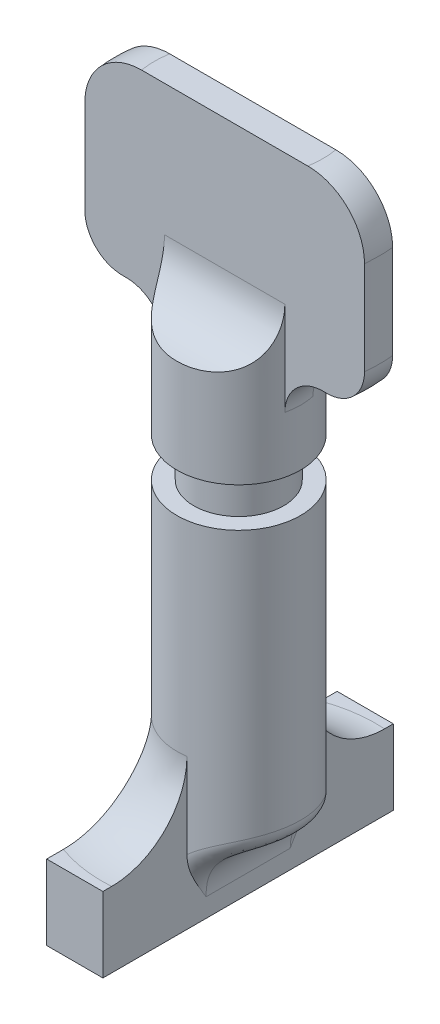
SolidWorks part; units mm, degrees
ref_plane "Front Plane" through (0, 0, 0) normal (0, 0, 1) x (1, 0, 0)
ref_plane "Top Plane" through (0, 0, 0) normal (0, 1, 0) x (1, 0, 0)
ref_plane "Right Plane" through (0, 0, 0) normal (1, 0, 0) x (0, 0, -1)
sketch "Sketch1" plane through (0, 0, 0) normal (0, 0, 1) x (1, 0, 0)
  line L0 (3.3, 27) -> (3.3, 22)
  line L1 (3.3, 22) -> (2.4, 22)
  line L2 (2.4, 22) -> (2.4, 19.9)
  line L3 (2.4, 19.9) -> (3.3, 19.9)
  line L4 (3.3, 19.9) -> (3.3, 5)
  line L5 (3.3, 5) -> (0, 5)
  line L6 (3.3, 27) -> (0, 27)
  line L7 (0, 27) -> (0, 5)
  dimension "D1" = 22
  dimension "D2" = 2.1
  dimension "D3" = 5
  dimension "D4" = 5
  dimension "D5" = 3.3
  dimension "D6" = 2.4
revolve "Revolve1" add sketch "Sketch1" angle 360 about L7
sketch "Sketch2" plane through (0, 27, 0) normal (0, 1, 0) x (1, 0, 0)
  line L1 (-11.4046, 0.75) -> (11.4046, 0.75)
  line L2 (-11.4046, 0.75) -> (-11.4046, -0.75)
  line L3 (-11.4046, -0.75) -> (11.4046, -0.75)
  line L4 (11.4046, 0.75) -> (11.4046, -0.75)
  line L5 (-11.4046, 0.75) -> (11.4046, -0.75) construction
  line L6 (-11.4046, -0.75) -> (11.4046, 0.75) construction
  circle A0 centre (0, 0) radius 3.3
  circle A1 centre (0, 0) radius 7.5
  circle A2 centre (0, 0) radius 3.3 construction
  circle M3 centre (0, 0) radius 3.3
  dimension "D2" = 15
  dimension "D1" = 1.5
extrude "Boss-Extrude1" add sketch "Sketch2" along normal blind 10 contours L3 L1 M3 | L1 A1 L3 M3 | L3 A1 L1 M3 region at (-5.3794, 27, 0) region at (0, 27, 0) region at (5.3794, 27, 0)
fillet "Fillet2" radius 2 4 edges at (7.5, 27, 0) (-7.5, 27, 0) (-3.3, 27, 0) (3.3, 27, 0)
fillet "Fillet3" radius 3 4 edges at (-7.5, 37, 0) (7.5, 37, 0) (0, 27, -0.75) (0, 27, 0.75)
sketch "Sketch21" plane through (0, 0, 0) normal (0, 1, 0) x (1, 0, 0)
  line L0 (0.5, 8.3) -> (0.5, -8.3) construction
  line L1 (0.5, -8.3) -> (-2.5, -8.3) construction
  line L2 (-2.5, -8.3) -> (-2.5, 8.3) construction
  line L3 (-2.5, 8.3) -> (0.5, 8.3) construction
  circle A0 centre (0, 0) radius 8 construction
  point P5 (0.5, 0)
  dimension "D1" = 16
  dimension "D2" = 16.6
  dimension "D3" = 3
  dimension "D4" = 8.5
sketch "Sketch5" plane through (0, 5, 0) normal (0, -1, 0) x (1, 0, 0)
  line L1 (-1.925, -7.75) -> (-0.075, -7.75) construction
  line L2 (-1.925, -7.75) -> (-1.925, 7.75) construction
  line L3 (-1.925, 7.75) -> (-0.075, 7.75) construction
  line L4 (-0.075, -7.75) -> (-0.075, 7.75) construction
  line L5 (-0.075, 0) -> (-1.925, 0) construction
  line L6 (-1, 23.25) -> (-1, -7.75) construction
  line L11 (-2.5, -8.3) -> (0.5, -8.3) construction
  line L12 (0.5, 7.75) -> (-2.5, 7.75)
  line L13 (-2.5, 7.75) -> (-2.5, -7.75)
  line L14 (-2.5, -7.75) -> (0.5, -7.75)
  line L15 (0.5, -7.75) -> (0.5, 7.75)
  point P0 (0, 0)
  point P5 (0, 0)
  point P13 (-1, -8.3)
  point P21 (-1, 7.75)
  dimension "D4" = 3
  dimension "D1" = 1.85
  dimension "D2" = 15.5
extrude "Boss-Extrude2" add sketch "Sketch5" along normal offset from surface (4 mm away) 1 up to plane "Top Plane"
fillet "Fillet5" radius 3 1 edges at (0.5, 5, 0)
fillet "Fillet4" radius 4 2 edges at (-1.1432, 5, -3.0957) (-1.1432, 5, 3.0957)
fillet "Fillet6" radius 1 2 edges at (-3.3, 5, 0) (3.3, 4.9933, 0)
